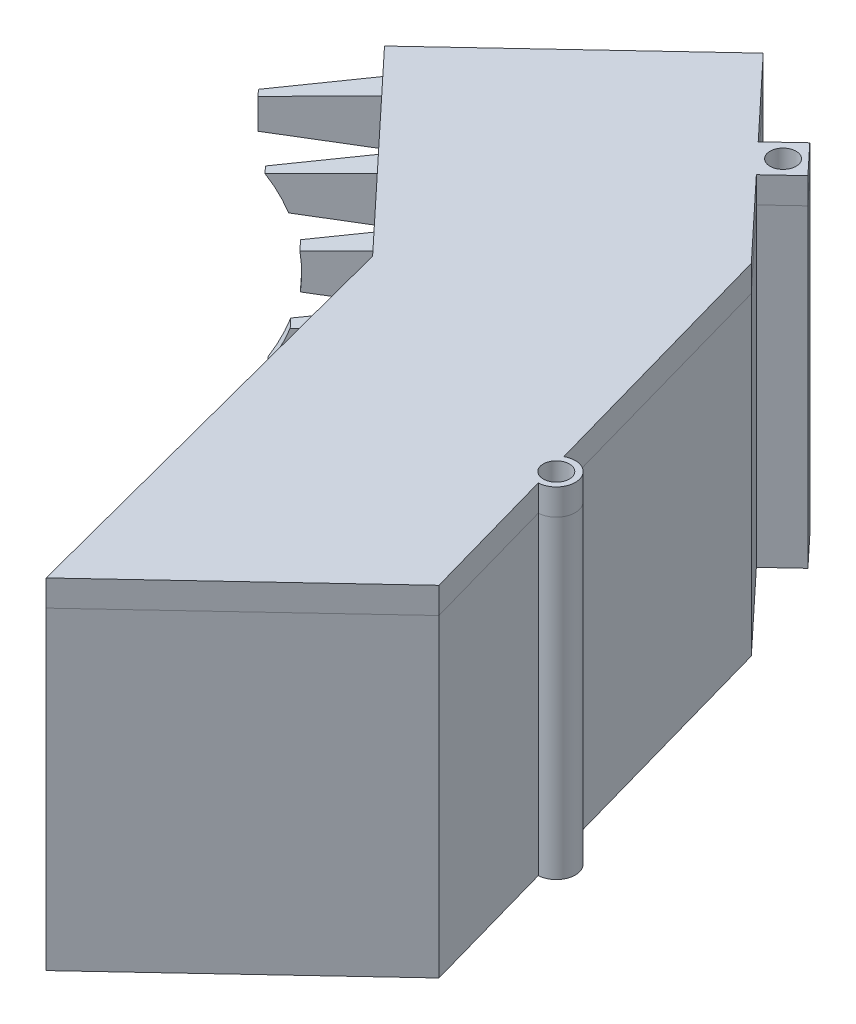
SolidWorks part; units mm, degrees
ref_plane "Front Plane" through (0, 0, 0) normal (0, 0, 1) x (1, 0, 0)
ref_plane "Top Plane" through (0, 0, 0) normal (0, 1, 0) x (1, 0, 0)
ref_plane "Right Plane" through (0, 0, 0) normal (1, 0, 0) x (0, 0, -1)
sketch "Sketch1" plane through (0, 0, 0) normal (0, 1, 0) x (1, 0, 0)
  line L0 (-4.2088, -43.4753) -> (11.4751, 13.8639) construction
  line L1 (15.2438, 108.2324) -> (-2.7837, 127.4797) construction
  line L2 (-27.496, 153.8638) -> (-74.9669, 109.4011) construction
  line L3 (11.4751, 13.8639) -> (-32.8086, 77.4293) construction
  line L4 (15.2438, 108.2324) -> (33.1183, 44.8363) construction
  line L5 (45.0177, 2.6318) -> (-4.2088, -43.4753) construction
  line L6 (-4.2088, -43.4753) -> (-32.2271, 63.7697) construction
  line L7 (45.0177, 2.6318) -> (35.5507, 36.2092)
  line L8 (15.2438, 108.2324) -> (-2.7837, 127.4797)
  line L9 (-27.496, 153.8638) -> (-74.9669, 109.4011)
  line L10 (-74.9669, 109.4011) -> (-32.2271, 63.7697)
  line L11 (-32.2271, 63.7697) -> (-4.2088, -43.4753)
  line L13 (45.0177, 2.6318) -> (-4.2088, -43.4753)
  line L15 (35.5507, 36.2092) -> (45.0177, 2.6318) construction
  line L16 (33.1183, 44.8363) -> (15.2438, 108.2324)
  line L17 (-32.8086, 77.4293) -> (-1.2, 109.0418) construction
  line L18 (20.4045, -20.4217) -> (11.4751, 13.8639) construction
  line L19 (-4.2088, -43.4753) -> (-17.3046, 6.6513) construction
  line L20 (0.3363, 130.3833) -> (0.3273, 130.3935) construction
  line L21 (-17.3046, 6.6513) -> (11.4751, 13.8639) construction
  line L22 (-6.1168, 137.7559) -> (-9.4684, 134.6166) construction
  line L23 (-3.0026, 140.4816) -> (-2.8851, 140.5844) construction
  line L24 (-17.3046, 6.6513) -> (-13.163, 7.6893) construction
  line L25 (-13.163, 7.6893) -> (-27.9465, 65.5328) construction
  line L26 (3.679, 133.5328) -> (-2.7837, 127.4797)
  line L27 (3.679, 133.5328) -> (-3.0057, 140.6698)
  line L29 (-3.0057, 140.6698) -> (-9.4684, 134.6166)
  line L30 (-51.2315, 131.6325) -> (-48.4968, 128.2564) construction
  line L31 (-48.4968, 128.2564) -> (-27.496, 147.9264) construction
  line L32 (-9.4684, 134.6166) -> (-27.496, 153.8638) construction
  line L33 (-9.4684, 134.6166) -> (-27.496, 153.8638)
  line L34 (-3.0026, 140.4816) -> (-3.0057, 140.6698) construction
  line L35 (-27.496, 147.9264) -> (-23.2222, 143.3634) construction
  line L36 (0.3273, 130.3935) -> (0.3363, 130.3833) construction
  line L37 (-23.2222, 143.3634) -> (-20.2598, 146.1381) construction
  line L38 (-23.2222, 143.3634) -> (9.6827, 108.2324) construction
  line L39 (24.1811, 76.5343) -> (20.2695, 75.4315) construction
  line L40 (20.2695, 75.4315) -> (13.2737, 100.2435) construction
  line L41 (20.2695, 75.4315) -> (27.658, 49.2262) construction
  line L42 (27.658, 49.2262) -> (31.4686, 35.7107) construction
  line L43 (31.4686, 35.7107) -> (34.5448, 24.4916) construction
  line L44 (12.1112, 105.39) -> (13.2737, 100.2435) construction
  line L45 (9.6827, 108.2324) -> (12.1112, 105.39) construction
  line L46 (-53.597, 86.5854) -> (-50.4371, 89.545) construction
  line L47 (-50.4371, 89.545) -> (-71.8071, 112.3607) construction
  line L48 (-48.4968, 128.2564) -> (-68.8447, 109.1979) construction
  line L49 (-68.8447, 109.1979) -> (-50.4371, 89.545) construction
  line L50 (-50.4371, 89.545) -> (-27.9465, 65.5328) construction
  line L51 (-68.8447, 109.1979) -> (-27.9465, 65.5328)
  line L52 (-27.9465, 65.5328) -> (-13.163, 7.6893)
  line L53 (-68.8447, 109.1979) -> (-27.496, 147.9264)
  line L54 (-27.496, 147.9264) -> (12.1112, 105.39)
  line L55 (12.1112, 105.39) -> (34.5448, 24.4916)
  arc A1 (35.5507, 36.2092) -> (33.1183, 44.8363) centre (35.3343, 40.8046) ccw
  circle A4 centre (-2.8946, 134.0748) radius 3.175
  circle A5 centre (35.3343, 40.8046) radius 3.175
  circle A6 centre (11.4751, 13.8639) radius 25.4
  circle A7 centre (-32.8086, 77.4293) radius 3.175
  circle A8 centre (-1.2, 109.0418) radius 3.175
  point P30 (0, 0)
  dimension "D1" = 6.35
  dimension "D2" = 6.35
  dimension "D3" = 59.4455
  dimension "D5" = 50.8
  dimension "D8" = 6.35
  dimension "D4" = 31.576
  dimension "D6" = 77.47
  dimension "D7" = 129.839
  dimension "D9" = 44.704
  dimension "D10" = 100.14
  dimension "D11" = 35.4294
  dimension "D12" = 4.2697
ref_plane "Plane1" through (0, 0, 0) normal (0, 1, 0) x (1, 0, 0)
sketch "Sketch4" plane through (0, 0, 0) normal (0, 1, 0) x (1, 0, 0)
  line L0 (-68.8447, 109.1979) -> (-27.9465, 65.5328)
  line L1 (-27.9465, 65.5328) -> (-13.1495, 7.6432)
  line L2 (-68.8447, 109.1979) -> (-27.496, 147.9264)
  line L3 (-27.496, 147.9264) -> (12.1112, 105.39)
  line L4 (12.1112, 105.39) -> (34.5583, 24.4455)
  circle A0 centre (-2.8946, 134.0748) radius 3.175
  circle A1 centre (35.3343, 40.8046) radius 3.175
  circle A2 centre (11.4751, 13.8639) radius 25.393
  circle A3 centre (-32.8086, 77.4293) radius 3.175
  circle A4 centre (-1.2, 109.0418) radius 3.175
  point P16 (-27.496, 147.9264)
  point P18 (-68.8447, 109.1979)
  point P20 (-27.9465, 65.5328)
  point P22 (35.3343, 40.8046)
  point P24 (12.1112, 105.39)
  point P26 (-2.8946, 134.0748)
  point P28 (-1.2, 109.0418)
  point P30 (-32.8086, 77.4293)
  point P32 (11.4751, 13.8639)
extrude "Boss-Extrude2" add sketch "Sketch1" along normal blind 76.2 contours L7 A1 L16 L8 L26 L27 L29 L33 L9 L10 L11 L13 A6 L52 L51 L53 L54 L55 A5 A4 region at (18.8257, 0, 18.7361)
extrude "Boss-Extrude3" add sketch "Sketch1<5>" along normal blind 6.35 contours A6 L55 L54 L53 L51 L52 A8 A7 region at (-15.1101, 0, -86.0279)
sketch "Sketch1<5>" plane through (0, 0, 0) normal (0, 1, 0) x (1, 0, 0) same geometry as "Sketch1"
ref_plane "Plane2" through (0, 76.2, 0) normal (0, 1, 0) x (1, 0, 0)
sketch "Sketch5" plane through (0, 76.2, 0) normal (0, 1, 0) x (1, 0, 0)
  line L0 (45.0177, 2.6318) -> (35.5507, 36.2092)
  line L1 (15.2438, 108.2324) -> (-2.7837, 127.4797)
  line L2 (-27.496, 153.8638) -> (-74.9669, 109.4011)
  line L3 (-74.9669, 109.4011) -> (-32.2271, 63.7697)
  line L4 (-32.2271, 63.7697) -> (-4.2088, -43.4753)
  line L5 (45.0177, 2.6318) -> (-4.2088, -43.4753)
  line L6 (33.1183, 44.8363) -> (15.2438, 108.2324)
  line L7 (3.679, 133.5328) -> (-2.7837, 127.4797)
  line L8 (3.679, 133.5328) -> (-3.0057, 140.6698)
  line L9 (-3.0057, 140.6698) -> (-9.4684, 134.6166)
  line L10 (-9.4684, 134.6166) -> (-27.496, 153.8638)
  line L11 (45.0177, 2.6318) -> (35.5507, 36.2092) construction
  line L12 (-74.9669, 109.4011) -> (-32.2271, 63.7697) construction
  circle A1 centre (-2.8946, 134.0748) radius 3.175
  arc A3 (35.5507, 36.2092) -> (33.1183, 44.8363) centre (35.3343, 40.8046) ccw construction
  arc A4 (35.5507, 36.2092) -> (33.1183, 44.8363) centre (35.3343, 40.8046) ccw
  circle A5 centre (35.3343, 40.8046) radius 3.175
extrude "Boss-Extrude4" add sketch "Sketch5" along normal blind 6.35 separate body
ref_plane "Plane3" through (14.6497, 0, -13.7214) normal (-0.7299, 0, 0.6836) x (0.6836, 0, 0.7299)
sketch "Sketch6" plane through (14.6497, 0, -13.7214) normal (-0.7299, 0, 0.6836) x (0.6836, 0, 0.7299)
  line L0 (-99.8337, 82.55) -> (-99.8337, 0) construction
  line L4 (-99.8337, 66.675) -> (-99.8337, 15.875) construction
  line L6 (-125.2337, 66.675) -> (-74.4337, 66.675)
  line L7 (-125.2337, 66.675) -> (-125.2337, 15.875)
  line L8 (-125.2337, 15.875) -> (-74.4337, 15.875)
  line L9 (-74.4337, 66.675) -> (-74.4337, 15.875)
  line L11 (-131.0944, 82.55) -> (-68.573, 82.55) construction
  line L12 (65.9916, 0) -> (-65.9916, 0) construction
  line L13 (-131.0944, 38.1) -> (-68.573, 38.1) construction
  line L14 (-131.0944, 76.2) -> (-131.0944, 0) construction
  line L15 (-68.573, 76.2) -> (-68.573, 0) construction
  line L16 (-125.2337, 41.275) -> (-74.4337, 41.275) construction
  point P4 (-99.8337, 82.55)
  point P6 (-131.0944, 41.275)
  point P20 (-99.8337, 41.275)
  point P23 (-99.8337, 41.275)
  dimension "D1" = 50.8
  dimension "D2" = 50.8
extrude "Cut-Extrude1" cut sketch "Sketch6" against normal blind 21.59
sketch "Sketch7" plane through (14.6497, 0, -13.7214) normal (-0.7299, 0, 0.6836) x (0.6836, 0, 0.7299)
  line L0 (-125.2337, 66.675) -> (-125.2337, 15.875) construction
  line L1 (-131.0944, 76.1681) -> (-125.2337, 76.1681)
  line L2 (-131.0944, 76.1681) -> (-131.0944, 65.0458)
  line L3 (-131.0944, 65.0458) -> (-125.2337, 65.0458)
  line L4 (-125.2337, 76.1681) -> (-125.2337, 65.0458)
  line L5 (-131.0944, 48.7843) -> (-125.2337, 48.7843)
  line L6 (-125.2337, 59.9067) -> (-125.2337, 48.7843)
  line L7 (-131.0944, 59.9067) -> (-125.2337, 59.9067)
  line L8 (-131.0944, 59.9067) -> (-131.0944, 48.7843)
  line L9 (-131.0944, 32.5229) -> (-125.2337, 32.5229)
  line L10 (-125.2337, 43.6452) -> (-125.2337, 32.5229)
  line L11 (-131.0944, 43.6452) -> (-125.2337, 43.6452)
  line L12 (-131.0944, 43.6452) -> (-131.0944, 32.5229)
  line L13 (-131.0944, 16.2614) -> (-125.2337, 16.2614)
  line L14 (-125.2337, 27.3838) -> (-125.2337, 16.2614)
  line L15 (-131.0944, 27.3838) -> (-125.2337, 27.3838)
  line L16 (-131.0944, 27.3838) -> (-131.0944, 16.2614)
  line L17 (-131.0944, 0) -> (-125.2337, 0)
  line L18 (-125.2337, 11.1223) -> (-125.2337, 0)
  line L19 (-131.0944, 11.1223) -> (-125.2337, 11.1223)
  line L20 (-131.0944, 11.1223) -> (-131.0944, 0)
  line L21 (-131.0944, 0) -> (-68.573, 0) construction
  line L22 (-131.0944, 76.2) -> (-131.0944, 0) construction
  point P7 (0, 0)
  point P26 (-131.0944, 76.0946)
  point P29 (-131.0944, 76.1681)
  dimension "D2" = 5
extrude "Boss-Extrude5" add sketch "Sketch7" along normal blind 21.59 draft 5
ref_plane "Plane4" through (-89.6167, 0, -95.6796) normal (-0.6836, 0, -0.7299) x (-0.7299, 0, 0.6836)
sketch "Sketch10" plane through (-89.6167, 0, -95.6796) normal (-0.6836, 0, -0.7299) x (-0.7299, 0, 0.6836)
  circle A0 centre (30.057, 37.7452) radius 36.0519
  point P0 (30.057, 37.7452)
extrude "Cut-Extrude2" cut sketch "Sketch10" against normal blind 21.59
